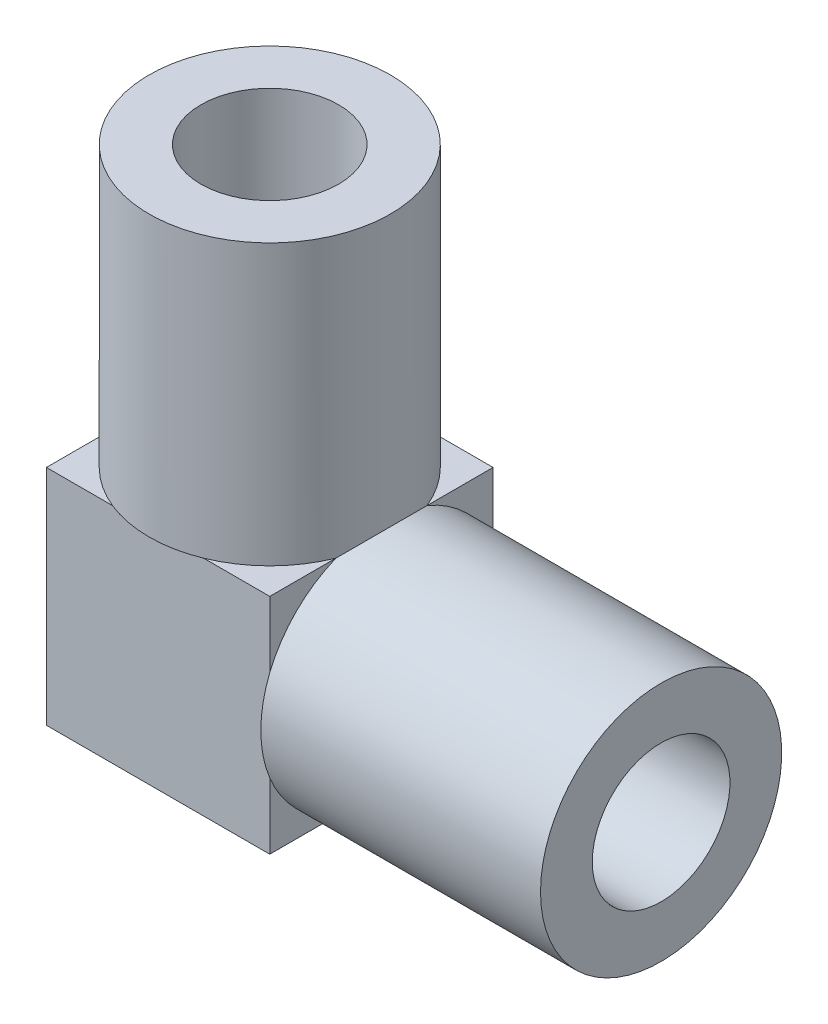
SolidWorks part; units mm, degrees
ref_plane "Front Plane" through (0, 0, 0) normal (0, 0, 1) x (1, 0, 0)
ref_plane "Top Plane" through (0, 0, 0) normal (0, 1, 0) x (1, 0, 0)
ref_plane "Right Plane" through (0, 0, 0) normal (1, 0, 0) x (0, 0, -1)
sketch "Block Sketch" plane through (0, 0, 0) normal (0, 0, 1) x (1, 0, 0)
  line L0 (-10.3, -10.3) -> (10.3, -10.3)
  line L1 (10.3, -10.3) -> (10.3, 10.3)
  line L2 (10.3, 10.3) -> (-10.3, 10.3)
  line L3 (-10.3, 10.3) -> (-10.3, -10.3)
extrude "Block" add sketch "Block Sketch" along normal mid plane 20.6
ref_axis "Engine Axis" through (38.4612, 0, 0) along (-1, 0, 0)
ref_axis "Stem Axis" through (0, -13.4852, 0) along (0, 1, 0)
sketch "Arm X Sketch" plane through (0, 0, 0) normal (0, 0, 1) x (1, 0, 0)
  line L0 (-1000, 0) -> (1000, 0) construction
  line L1 (10.3, 0) -> (36.1, 0)
  line L2 (36.1, 0) -> (36.1, 11.124)
  line L3 (36.1, 11.124) -> (10.3, 11.124)
  line L4 (10.3, 11.124) -> (10.3, 0)
revolve "Arm X" add sketch "Arm X Sketch" angle 360 about L0
sketch "Arm Y Sketch" plane through (0, 0, 0) normal (0, 0, 1) x (1, 0, 0)
  line L0 (0, -500) -> (0, 500) construction
  line L1 (0, 10.3) -> (11.124, 10.3)
  line L2 (11.124, 10.3) -> (11.124, 36.1)
  line L3 (11.124, 36.1) -> (0, 36.1)
  line L4 (0, 36.1) -> (0, 10.3)
revolve "Arm Y" add sketch "Arm Y Sketch" angle 360 about L0
sketch "Socket X Sketch" plane through (0, 0, 0) normal (0, 0, 1) x (1, 0, 0)
  line L0 (-1000, 0) -> (1000, 0) construction
  line L1 (13.2, 0) -> (37.1, 0)
  line L2 (37.1, 0) -> (37.1, 6.35)
  line L3 (37.1, 6.35) -> (13.2, 6.35)
  line L4 (13.2, 6.35) -> (13.2, 0)
revolve "Socket X" cut sketch "Socket X Sketch" angle 360 about L0
sketch "Socket Y Sketch" plane through (0, 0, 0) normal (0, 0, 1) x (1, 0, 0)
  line L0 (0, -500) -> (0, 500) construction
  line L1 (0, 13.2) -> (6.35, 13.2)
  line L2 (6.35, 13.2) -> (6.35, 37.1)
  line L3 (6.35, 37.1) -> (0, 37.1)
  line L4 (0, 37.1) -> (0, 13.2)
revolve "Socket Y" cut sketch "Socket Y Sketch" angle 360 about L0
